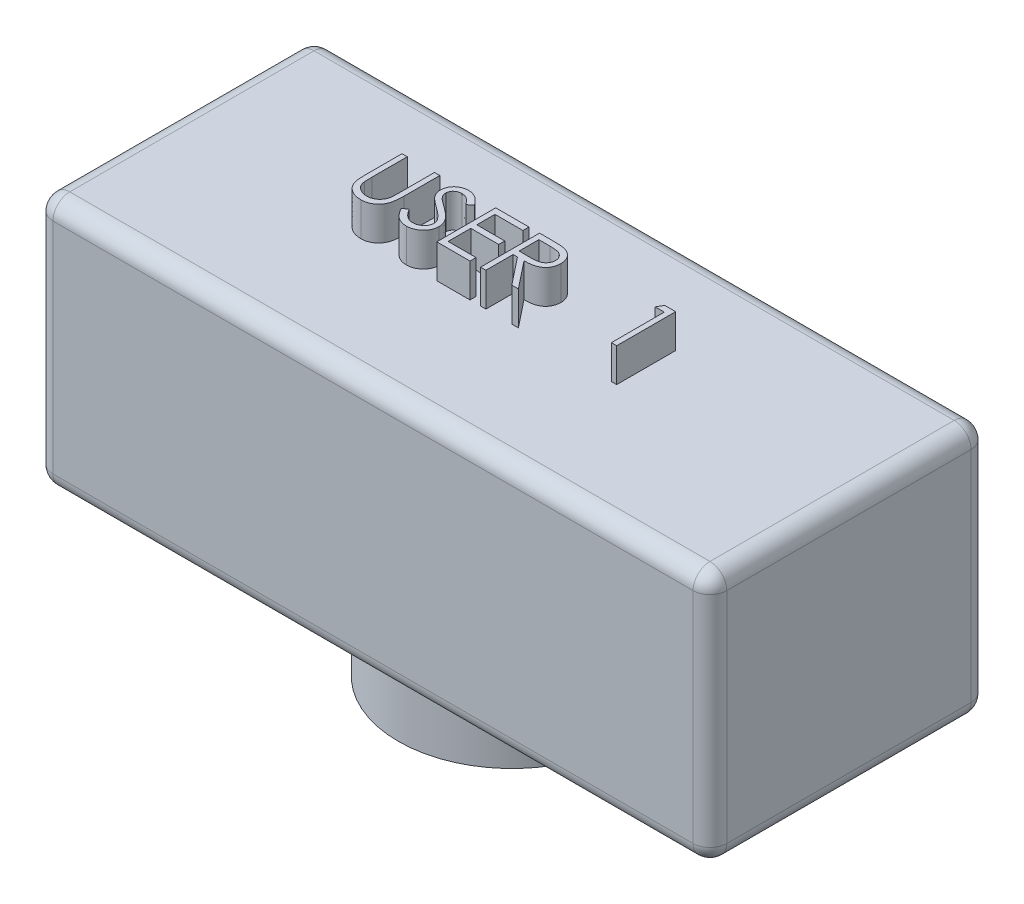
SolidWorks part; units mm, degrees
ref_plane "Front Plane" through (0, 0, 0) normal (0, 0, 1) x (1, 0, 0)
ref_plane "Top Plane" through (0, 0, 0) normal (0, 1, 0) x (1, 0, 0)
ref_plane "Right Plane" through (0, 0, 0) normal (1, 0, 0) x (0, 0, -1)
sketch "Sketch1" plane through (0, 0, 0) normal (0, 1, 0) x (1, 0, 0)
  circle A0 centre (0, 0) radius 5.75
extrude "Boss-Extrude1" add sketch "Sketch1" along normal blind 4.5
sketch "Sketch2" plane through (0, 4.5, 0) normal (0, 1, 0) x (1, 0, 0)
  line L1 (-20, 8.25) -> (20, 8.25)
  line L2 (-20, 8.25) -> (-20, -8.25)
  line L3 (-20, -8.25) -> (20, -8.25)
  line L4 (20, 8.25) -> (20, -8.25)
  line L5 (-20, 8.25) -> (20, -8.25) construction
  line L6 (-20, -8.25) -> (20, 8.25) construction
  point P0 (0, 0)
extrude "Boss-Extrude2" add sketch "Sketch2" along normal blind 15
sketch "Sketch3" plane through (0, 4.5, 0) normal (0, -1, 0) x (1, 0, 0)
  circle A0 centre (0, 0) radius 6.75
extrude "Boss-Extrude3" add sketch "Sketch3" along normal blind 4
sketch "Sketch5" plane through (0, 0, 0) normal (0, -1, 0) x (1, 0, 0)
  circle A0 centre (0, 0) radius 5.75
extrude "Cut-Extrude1" cut sketch "Sketch5" against normal blind 4
fillet "Fillet1" radius 1 4 edges at (20, 19.5, 0) (0, 19.5, 8.25) (-20, 19.5, 0) (0, 19.5, -8.25)
sketch "Sketch9" plane through (0, 19.5, 0) normal (0, 1, 0) x (1, 0, 0)
  text T0 "USER   1" font "Century Gothic" height 3.5
extrude "Boss-Extrude5" add sketch "Sketch9" along normal blind 2
fillet "Fillet2" radius 1 12 edges at (19.7071, 19.2071, -7.9571) (19.7071, 19.2071, 7.9571) (-19.7071, 19.2071, 7.9571) (-19.7071, 19.2071, -7.9571) (0, 4.5, -8.25) (20, 11.5, -8.25) (20, 4.5, 0) (20, 11.5, 8.25) (0, 4.5, 8.25) (-20, 11.5, 8.25) (-20, 4.5, 0) (-20, 11.5, -8.25)
